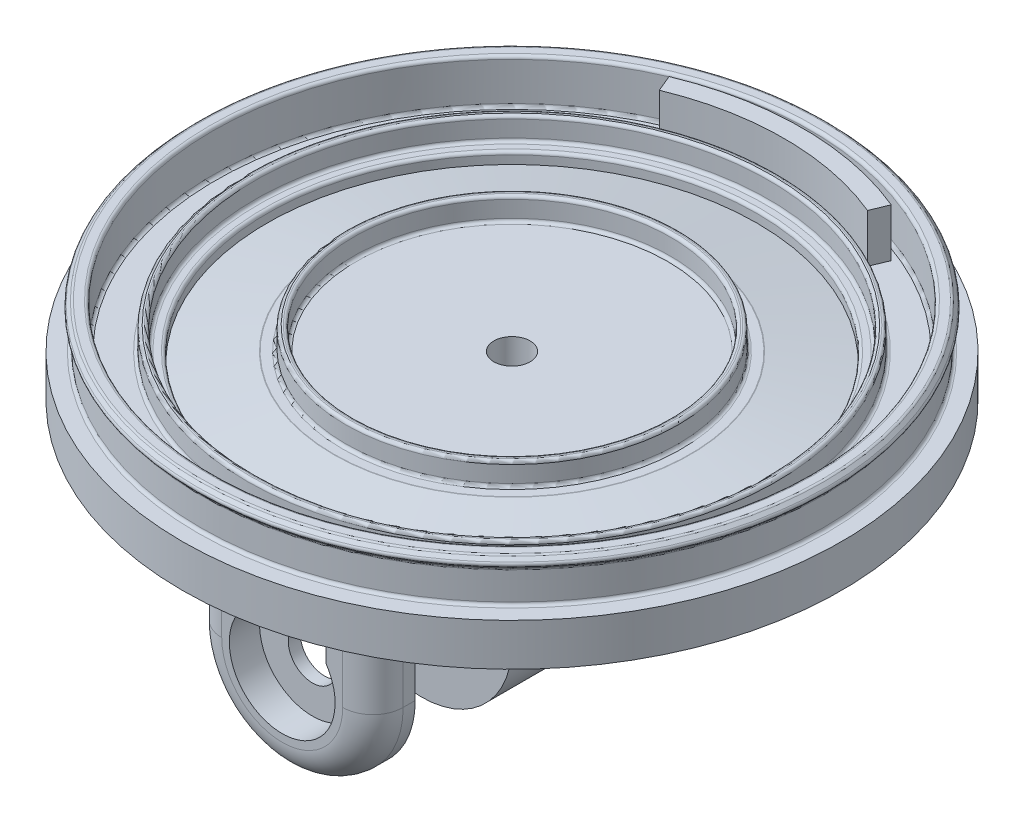
SolidWorks part; units mm, degrees
material "PLA"
ref_plane "Front Plane" through (0, 0, 0) normal (0, 0, 1) x (1, 0, 0)
ref_plane "Top Plane" through (0, 0, 0) normal (0, 1, 0) x (1, 0, 0)
ref_plane "Right Plane" through (0, 0, 0) normal (1, 0, 0) x (0, 0, -1)
sketch "Sketch2" plane through (0, 0, 0) normal (0, 1, 0) x (1, 0, 0)
  circle A0 centre (0, 0) radius 54.5
  dimension "D1" = 109
extrude "Boss-Extrude1" add sketch "Sketch2" along normal blind 7
sketch "Sketch3" plane through (0, 0, 0) normal (0, 0, 1) x (1, 0, 0)
  line L0 (0, 0) -> (0, 7) construction
  line L1 (54.5, 7) -> (-54.5, 7) construction
  line L2 (0, 7) -> (-29.5, 7) construction
  line L3 (-29.5, 7) -> (-40.5, 7)
  line L4 (-40.5, 7) -> (-40.5, 5.127)
  line L5 (-40.5, 5.127) -> (-29.5, 7)
  dimension "D1" = 29.5
  dimension "D2" = 11
  dimension "D3" = 1.873
revolve "Cut-Revolve1" cut sketch "Sketch3" angle 360 about L0
sketch "Sketch4" plane through (0, 7, 0) normal (0, 1, 0) x (1, 0, 0)
  circle A0 centre (0, 0) radius 43.75
  circle A1 centre (0, 0) radius 42.5
  circle A2 centre (0, 0) radius 27.5
  circle A3 centre (0, 0) radius 26.25
  dimension "D1" = 87.5
  dimension "D2" = 85
  dimension "D3" = 55
  dimension "D4" = 52.5
extrude "Boss-Extrude2" add sketch "Sketch4" along normal blind 3.723 contours A0 A1 | A2 A3 region at (-42.5126, 7, 0) region at (-26.7222, 7, 0)
fillet "Fillet1" radius 0.5 10 edges at (0, 7, 26.25) (0, 7, -29.5) (0, 7, -40.5) (0, 10.723, 43.75) (0, 7, 42.5) (0, 10.723, 42.5) (0, 7, 27.5) (0, 10.723, 27.5) (0, 10.723, 26.25) (0, 7, 43.75)
sketch "Sketch5" plane through (0, 0, 0) normal (0, 0, 1) x (1, 0, 0)
  line L0 (0, 7) -> (-49.5, 7) construction
  line L1 (54.5, 7) -> (-54.5, 7) construction
  line L2 (0, 7) -> (0, 24.3916) construction
  line L3 (0, -55) -> (0, 55) construction
  line L4 (-49.5, 7) -> (-51.5, 7)
  line L5 (-51.5, 7) -> (-51.5, 12.323)
  line L6 (-51.5, 12.323) -> (-52.5, 13.323)
  line L7 (-52.5, 13.323) -> (-51.5, 14.323)
  line L8 (-51.5, 14.323) -> (-49.5, 14.323)
  line L9 (-49.5, 14.323) -> (-49.5, 7)
  dimension "D1" = 7.323
  dimension "D2" = 1
  dimension "D3" = 1
  dimension "D4" = 2
  dimension "D5" = 2
  dimension "D6" = 49.5
revolve "Revolve1" add sketch "Sketch5" angle 360 about L2
fillet "Fillet2" radius 0.5 6 edges at (51.5, 7, 0) (49.5, 7, 0) (49.5, 14.323, 0) (51.5, 14.323, 0) (51.5, 12.323, 0) (52.5, 13.323, 0)
sketch "Sketch6" plane through (0, 7, 0) normal (0, 1, 0) x (1, 0, 0)
  circle A0 centre (0, 0) radius 3
  dimension "D1" = 6
extrude "Cut-Extrude1" cut sketch "Sketch6" against normal blind 6
sketch "Sketch7" plane through (0, 0, 0) normal (0, 0, 1) x (1, 0, 0)
  line L0 (-54.5, 0) -> (54.5, 0) construction
  line L1 (-15, 0) -> (15, 0)
  line L2 (-15, 0) -> (-15, -20)
  line L3 (-15, -20) -> (15, -20)
  line L4 (15, 0) -> (15, -20)
  line L5 (-15, -20) -> (-11.025, -20)
  line L6 (11.025, -20) -> (15, -20)
  circle A0 centre (0, -20) radius 15
  circle A1 centre (0, -20) radius 11.025
  arc A2 (11.025, -20) -> (-11.025, -20) centre (0, -20) ccw
  circle A3 centre (0, -20) radius 4
  point P8 (0, 0)
  dimension "D1" = 30
  dimension "D3" = 22.05
  dimension "D4" = 8
  dimension "D2" = 20
extrude "Boss-Extrude3" add sketch "Sketch7" along normal blind 15 and the other way blind 15 contours A0 L4 L1 L2 | A1 L3 A0 | A1 L3 A0 | L3 A1 | L3 A1 region at (0, -4.7914, 0) region at (0, -5.3354, 0) region at (-13.0125, -20.3354, 0) region at (0, -14.8689, 0) region at (0, -25.1311, 0)
sketch "Sketch10" plane through (0, 0, 0) normal (0, 0, 1) x (1, 0, 0)
  line L0 (-54.5, 0) -> (54.5, 0) construction
  line L1 (20.9531, 0) -> (-17.5201, 0)
  line L2 (20.9531, 0) -> (20.9531, -42.1824)
  line L3 (20.9531, -42.1824) -> (-17.5201, -42.1824)
  line L4 (-17.5201, 0) -> (-17.5201, -42.1824)
extrude "Cut-Extrude4" cut sketch "Sketch10" against normal blind 5 and the other way blind 5
sketch "Sketch11" plane through (0, 0, 15) normal (0, 0, 1) x (1, 0, 0)
  line L0 (15, 0) -> (15, -20)
  line L1 (59.95, 0) -> (-59.95, 0) construction
  line L2 (15, 0) -> (15, -20) construction
  line L3 (-15, -20) -> (-15, 0)
  line L4 (-15, 0) -> (-15, -20) construction
  line L5 (-15, 0) -> (15, 0)
  arc A0 (15, -20) -> (-15, -20) centre (0, -20) cw
  circle A1 centre (0, -20) radius 3.5
  circle M5 centre (0, -20) radius 4
  arc M6 (-15, -20) -> (15, -20) centre (0, -20) ccw
  line M7 (15, -20) -> (15, 0)
  line M8 (15, 0) -> (-15, 0)
  line M9 (-15, 0) -> (-15, -20)
  dimension "D1" = 7
extrude "Boss-Extrude4" add sketch "Sketch11" along normal blind 2 from offset 16 contours M9 M6 M7 M8 M5 region at (0, -15.8479, 15)
sketch "Sketch12" plane through (0, 0, 33) normal (0, 0, 1) x (1, 0, 0)
  line L0 (-7.25, 0) -> (-7.25, -15.101)
  line L1 (59.95, 0) -> (-59.95, 0) construction
  line L2 (7.25, 0) -> (7.25, -15.101)
  line L3 (0, -27.1277) -> (0, 27.1277) construction
  line L4 (-7.25, 0) -> (7.25, 0)
  line L5 (-7.25, 0) -> (-15, 0)
  line L6 (-15, 0) -> (-15, -20) construction
  line L7 (7.25, 0) -> (15, 0)
  line L8 (15, -20) -> (15, 0) construction
  line L9 (15, 0) -> (15, -20)
  circle A0 centre (0, -20) radius 8.75
  arc A1 (15, -20) -> (-15, -20) centre (0, -20) cw
  arc A2 (-15, -20) -> (15, -20) centre (0, -20) ccw construction
  line M4 (-15, 0) -> (-15, -20)
  arc M5 (-15, -20) -> (15, -20) centre (0, -20) ccw
  line M6 (15, -20) -> (15, 0)
  line M7 (15, 0) -> (-15, 0)
  dimension "D1" = 17.5
  dimension "D2" = 14.5
  dimension "D3" = 7.25
extrude "Boss-Extrude5" add sketch "Sketch12" along normal blind 5 contours A0 L0 L2 M7 M4 M5 M6 region at (-7.711, -7.5505, 33)
fillet "Fillet3" radius 5 3 edges at (11.125, 0, 38) (-11.125, 0, 38) (-15, -10, 38)
sketch "Sketch13" plane through (0, 7, 0) normal (0, 1, 0) x (1, 0, 0)
  line L0 (18.3688, 44.3462) -> (17.2208, 41.5746)
  line L1 (-18.3688, 44.3462) -> (-17.2208, 41.5746)
  line L2 (-17.2208, 41.5746) -> (0, 0) construction
  line L3 (0, 0) -> (17.2208, 41.5746) construction
  line L4 (0, -27.1277) -> (0, 27.1277) construction
  arc A0 (17.2208, 41.5746) -> (-17.2208, 41.5746) centre (0, 0) ccw
  arc A1 (18.3688, 44.3462) -> (-18.3688, 44.3462) centre (0, 0) ccw
  point P7 (0, 48)
  dimension "D2" = 45
  dimension "D4" = 48
  dimension "D1" = 45
  dimension "D3" = 45
extrude "Boss-Extrude6" add sketch "Sketch13" along normal blind 8
